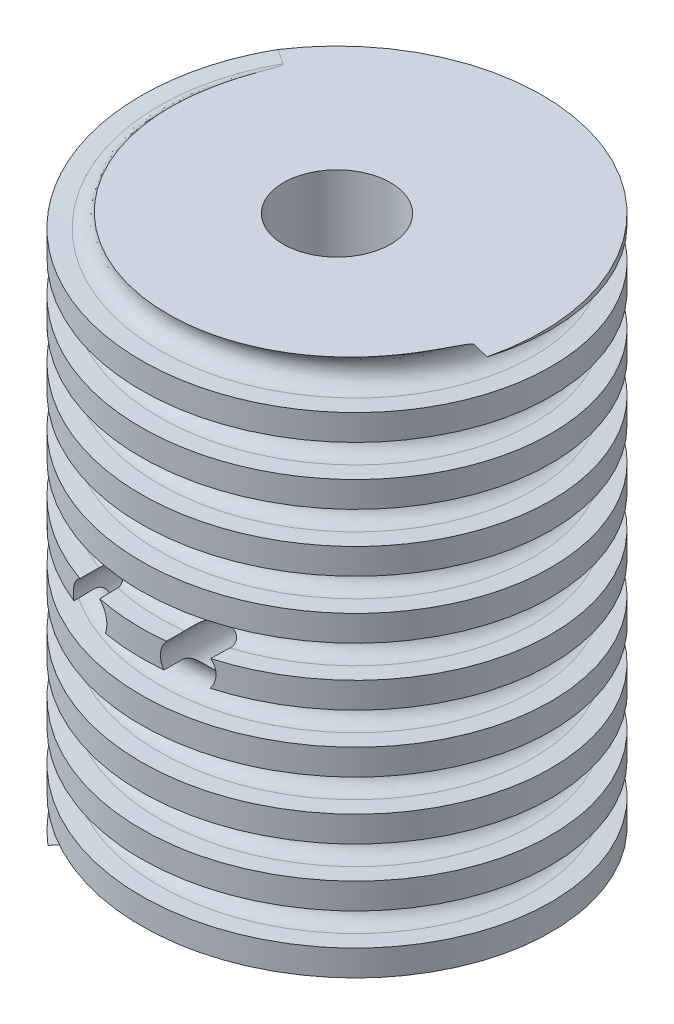
SolidWorks part; units mm, degrees
ref_plane "Front Plane" through (0, 0, 0) normal (0, 0, 1) x (1, 0, 0)
ref_plane "Top Plane" through (0, 0, 0) normal (0, 1, 0) x (1, 0, 0)
ref_plane "Right Plane" through (0, 0, 0) normal (1, 0, 0) x (0, 0, -1)
sketch "Sketch1" plane through (0, 0, 0) normal (0, 1, 0) x (1, 0, 0)
  circle A0 centre (0, 0) radius 11.5
  circle A1 centre (0, 0) radius 1.5
  dimension "D1" = 23
  dimension "D2" = 3
extrude "Boss-Extrude1" add sketch "Sketch1" along normal blind 30
sketch "Sketch3" plane through (0, 0, 0) normal (0, 0, 1) x (1, 0, 0)
  line L1 (-10.5, -1) -> (-20.5, -1)
  line L2 (-20.5, -1) -> (-20.5, -2.8)
  line L3 (-20.5, -2.8) -> (-10.5, -2.8)
  line L4 (0, 0) -> (0, -7.8644) construction
  line L5 (-11.5, 0) -> (11.5, 0) construction
  arc A0 (-10.5, -2.8) -> (-10.5, -1) centre (-10.5, -1.9) ccw
  dimension "D1" = 1.8
  dimension "D2" = 10
  dimension "D3" = 10.5
  dimension "D4" = 1
ref_plane "Plane1" through (0, -5, 0) normal (0, -1, 0) x (-1, 0, 0)
sketch "Sketch6" plane through (0, -5, 0) normal (0, -1, 0) x (1, 0, 0)
  circle A1 centre (0, 0) radius 10
  dimension "D1" = 20
curve "Helix/Spiral1" pitch 3.25 height 65 radius 10 left hand yes centre (0, -5, 0) axis (0, 1, 0) start towards (0, 0, -1)
sweep "Cut-Sweep1" cut profiles "Sketch3" path "Helix/Spiral1"
ref_plane "Plane2" through (0, 0, -11.5) normal (0, 0, 1) x (1, 0, 0)
sketch "Sketch7" plane through (0, 0, -11.5) normal (0, 0, 1) x (1, 0, 0)
  line L0 (0, 0) -> (0, 30) construction
  line L1 (11.5, 30) -> (-9.6136, 30) construction
  line L3 (4.78, 16.9) -> (-4.78, 16.9)
  line L4 (4.78, 16.9) -> (4.78, 13.1)
  line L5 (4.78, 13.1) -> (-4.78, 13.1)
  line L6 (-4.78, 16.9) -> (-4.78, 13.1)
  line L7 (4.78, 16.9) -> (-4.78, 13.1) construction
  line L8 (4.78, 13.1) -> (-4.78, 16.9) construction
  point P5 (0, 15)
  point P6 (0, 15)
  dimension "D1" = 9.56
  dimension "D2" = 3.8
extrude "Cut-Extrude1" cut sketch "Sketch7" along normal blind 6
sketch "Sketch9" plane through (0, 30, 0) normal (0, 1, 0) x (1, 0, 0)
  circle A0 centre (0, 0) radius 3
  dimension "D1" = 6
extrude "Cut-Extrude5" cut sketch "Sketch9" against normal blind 25
sketch "Sketch8" plane through (0, 0, -5.5) normal (0, 0, -1) x (-1, 0, 0)
  line L0 (4.78, 15) -> (-4.78, 15) construction
  line L1 (4.78, 16.9) -> (4.78, 13.1) construction
  line L2 (-4.78, 13.1) -> (-4.78, 16.9) construction
  circle A0 centre (-2.75, 15) radius 1.25
  circle A1 centre (2.75, 15) radius 1.25
  point P6 (0, 15)
  dimension "D1" = 2.5
  dimension "D2" = 2.75
  dimension "D3" = 2.75
extrude "Cut-Extrude6" cut sketch "Sketch8" against normal up to next
